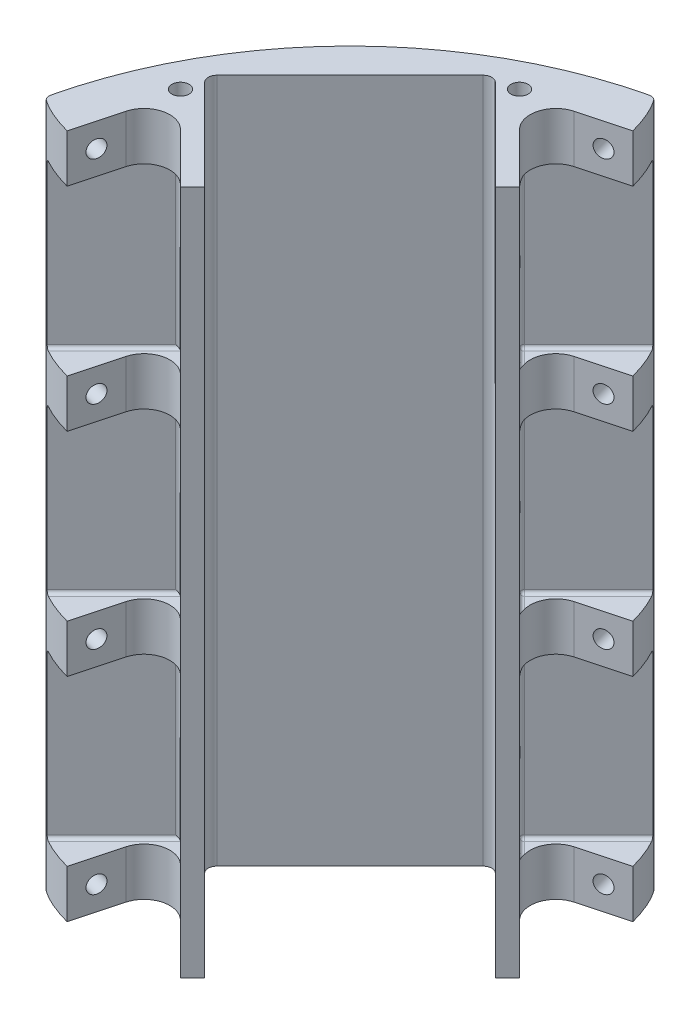
SolidWorks part; units mm, degrees
material "6061-T6 (SS)"
ref_plane "Front Plane" through (0, 0, 0) normal (0, 0, 1) x (1, 0, 0)
ref_plane "Top Plane" through (0, 0, 0) normal (0, 1, 0) x (1, 0, 0)
ref_plane "Right Plane" through (0, 0, 0) normal (1, 0, 0) x (0, 0, -1)
sketch "Constraints" plane through (0, 0, 0) normal (0, 1, 0) x (1, 0, 0)
  line L0 (0, 152.4) -> (0, -152.4) construction
  line L1 (-152.4, 0) -> (152.4, 0) construction
  circle A0 centre (0, 0) radius 152.4 construction
  circle A1 centre (0, 0) radius 149.225 construction
  circle A2 centre (0, 0) radius 12.7 construction
  circle A3 centre (0, 76.454) radius 12.7 construction
  circle A4 centre (76.454, 0) radius 12.7 construction
  circle A5 centre (0, -76.454) radius 12.7 construction
  circle A6 centre (-76.454, 0) radius 12.7 construction
  point P20 (0, 0)
  dimension "D1" = 25.4
  dimension "D4" = 304.8
  dimension "D3" = 76.454
  dimension "D2" = 3.175
  dimension "D6" = 76.454
  dimension "D7" = 76.454
  dimension "D5" = 4
sketch "Base" plane through (0, 0, 0) normal (0, 1, 0) x (1, 0, 0)
  line L0 (0, 76.454) -> (-76.454, 0) construction
  line L5 (21.8789, -21.8789) -> (-16.3481, 16.3481) construction
  line L9 (-27.6819, 146.635) -> (-55.7275, 118.5893)
  line L10 (-123.0795, 69.1979) -> (-87.1584, 33.2769)
  line L11 (-69.1979, 123.0795) -> (-123.0795, 69.1979)
  line L12 (-69.1979, 123.0795) -> (-33.2769, 87.1584)
  line L13 (-33.2769, 87.1584) -> (-28.7868, 91.6486)
  line L14 (-28.7868, 91.6486) -> (-55.7275, 118.5893)
  line L15 (-146.635, 27.6819) -> (-118.5893, 55.7275)
  line L16 (-91.6486, 28.7868) -> (-118.5893, 55.7275)
  line L17 (-87.1584, 33.2769) -> (-91.6486, 28.7868)
  line L18 (-19.5371, 78.1962) -> (-81.4004, 16.3329) construction
  arc A2 (-146.635, 27.6819) -> (-27.6819, 146.635) centre (0, 0) cw
  circle A3 centre (0, 0) radius 149.225 construction
  point P18 (-96.1387, 96.1387)
  dimension "D2" = 6.35
  dimension "D4" = 38.1
  dimension "D5" = 50.8
  dimension "D6" = 16.0528
  dimension "D3" = 76.2
  dimension "D1" = 68.619
extrude "Cradle" add sketch "Base" along normal blind 254 contours L9 L14 L13 L12 L11 L10 L17 L16 L15 A2
ref_plane "Mirror Plane 1" through (0, 127, 0) normal (0, 1, 0) x (1, 0, 0)
sketch "Sketch1" plane through (0, 254, 0) normal (0, 1, 0) x (1, 0, 0)
  line L1 (-69.1979, 123.0795) -> (-33.2769, 87.1584) construction
  line L2 (-69.1979, 123.0795) -> (-123.0795, 69.1979) construction
  line L3 (-69.1979, 123.0795) -> (-51.2374, 123.0795) construction
  line L4 (-96.1387, 96.1387) -> (-75.7363, 75.7363) construction
  line L5 (-27.6819, 146.635) -> (-55.7275, 118.5893) construction
  circle A0 centre (-60.2177, 123.0795) radius 3.175
  circle A2 centre (-123.0795, 60.2177) radius 3.175
  point P11 (-96.1387, 96.1387)
  dimension "D1" = 6.35
  dimension "D2" = 45
extrude "Cut-Extrude1" cut sketch "Sketch1" against normal blind 12.7 contours A2 | A0 region at (-123.0795, 254, -60.2177)
mirror "Mirror1" about plane through (0, 127, 0) normal (0, 1, 0) of "Cut-Extrude1"
ref_plane "Mirror Plane 2" through (0, 0, 0) normal (-0.7071, 0, 0.7071) x (0.7071, 0, 0.7071)
fillet "Eigth Inch Fillets (Internal)" radius 3.175 2 edges at (-123.0795, 127, -69.1979) (-69.1979, 127, -123.0795)
sketch "Sketch5" plane through (0, 0, 0) normal (0, -1, 0) x (1, 0, 0)
  line L0 (-1.749, -1.749) -> (-105.518, -105.518) construction
  line L1 (-159.3964, 6.0469) -> (-137.3575, -76.2032) construction
  line L2 (-131.3265, -0.5733) -> (-126.8165, -17.4048) construction
  line L3 (-71.443, -120.8344) -> (-120.8344, -71.443) construction
  line L4 (-116.9887, -31.347) -> (-128.5542, -34.446) construction
  line L5 (-126.122, -42.9979) -> (-130.7238, -25.8237)
  line L6 (-91.6486, -28.7868) -> (-118.5893, -55.7275) construction
  line L7 (-146.635, -27.6819) -> (-118.5893, -55.7275)
  line L8 (-118.5893, -55.7275) -> (-110.0025, -47.1408)
  arc A0 (-146.635, -27.6819) -> (-27.6819, -146.635) centre (0, 0) ccw construction
  circle A1 centre (0, 0) radius 152.4 construction
  circle A2 centre (0, 0) radius 149.225 construction
  arc A4 (-126.122, -42.9979) -> (-110.0025, -47.1408) centre (-116.8944, -40.5254) ccw
  arc A5 (-130.7238, -25.8237) -> (-146.635, -27.6819) centre (-145.018, 27.5232) cw
  point P4 (-53.6335, -53.6335)
  point P8 (-105.518, -105.518)
  point P11 (-96.1387, -96.1387)
  point P23 (-128.4229, -34.4108)
  line M18 (-118.5893, -55.7275) -> (-146.635, -27.6819)
  dimension "D1" = 304.8
  dimension "D2" = 25.4
  dimension "D3" = 5.9531
  dimension "D4" = 17.78
  dimension "D5" = 30
extrude "Radial Bolt Holder" add sketch "Sketch5" against normal blind 17.78 contours L5 A5 L8 A4 M18 region at (-131.0378, 0, -37.8112)
sketch "Sketch6" plane through (-128.4229, 0, -34.4108) normal (0.9659, 0, 0.2588) x (0.2588, 0, -0.9659)
  line L0 (-8.89, 17.78) -> (8.89, 0) construction
  circle A0 centre (0, 8.89) radius 3.175
  dimension "D1" = 6.35
extrude "Bolt Hole" cut sketch "Sketch6" against normal through all
pattern_linear "Pattern the Radial Bolt Holder" count 4 spacing 78.74 along (0, 1, 0) of "Radial Bolt Holder", "Bolt Hole"
mirror "Mirror Aforementioned Pattern" about plane through (0, 0, 0) normal (-0.7071, 0, 0.7071) of "Pattern the Radial Bolt Holder"
sketch "Sketch4" plane through (26.9408, 0, -26.9408) normal (-0.7071, 0, 0.7071) x (0.7071, 0, 0.7071)
  line L4 (-85.1607, 103.1875) -> (-85.1607, 150.8125) construction
  line L5 (-132.7857, 254) -> (-132.7857, 0) construction
  line L6 (-132.7857, 254) -> (-85.1607, 254) construction
  circle A0 centre (-108.9732, 127) radius 1.27
  circle A1 centre (-108.9732, 101.6) radius 1.27
  circle A2 centre (-108.9732, 76.2) radius 1.27
  circle A3 centre (-108.9732, 50.8) radius 1.27
  circle A4 centre (-108.9732, 25.4) radius 1.27
  circle A5 centre (-108.9732, 127) radius 1.27
  circle A6 centre (-108.9732, 101.6) radius 1.27
  circle A7 centre (-108.9732, 76.2) radius 1.27
  circle A8 centre (-108.9732, 50.8) radius 1.27
  circle A9 centre (-108.9732, 152.4) radius 1.27
  circle A10 centre (-108.9732, 127) radius 1.27
  circle A11 centre (-108.9732, 101.6) radius 1.27
  circle A12 centre (-108.9732, 76.2) radius 1.27
  circle A13 centre (-108.9732, 177.8) radius 1.27
  circle A14 centre (-108.9732, 152.4) radius 1.27
  circle A15 centre (-108.9732, 127) radius 1.27
  circle A16 centre (-108.9732, 101.6) radius 1.27
  circle A17 centre (-108.9732, 203.2) radius 1.27
  circle A18 centre (-108.9732, 177.8) radius 1.27
  circle A19 centre (-108.9732, 152.4) radius 1.27
  circle A20 centre (-108.9732, 127) radius 1.27
  circle A21 centre (-108.9732, 152.4) radius 1.27
  circle A22 centre (-108.9732, 177.8) radius 1.27
  circle A23 centre (-108.9732, 203.2) radius 1.27
  circle A25 centre (-96.2732, 25.4) radius 1.27
  circle A26 centre (-96.2732, 50.8) radius 1.27
  circle A27 centre (-96.2732, 76.2) radius 1.27
  circle A28 centre (-96.2732, 101.6) radius 1.27
  circle A29 centre (-96.2732, 127) radius 1.27
  circle A30 centre (-96.2732, 152.4) radius 1.27
  circle A31 centre (-96.2732, 177.8) radius 1.27
  circle A32 centre (-96.2732, 203.2) radius 1.27
  circle A33 centre (-96.2732, 228.6) radius 1.27
  circle A34 centre (-108.9732, 25.4) radius 1.27
  circle A35 centre (-108.9732, 50.8) radius 1.27
  circle A36 centre (-108.9732, 76.2) radius 1.27
  circle A37 centre (-108.9732, 101.6) radius 1.27
  circle A38 centre (-108.9732, 127) radius 1.27
  circle A39 centre (-108.9732, 152.4) radius 1.27
  circle A40 centre (-108.9732, 177.8) radius 1.27
  circle A41 centre (-108.9732, 203.2) radius 1.27
  circle A52 centre (-121.6732, 152.4) radius 1.27 [skipped]
  circle A53 centre (-121.6732, 177.8) radius 1.27 [skipped]
  circle A54 centre (-121.6732, 203.2) radius 1.27 [skipped]
  circle A55 centre (-108.9732, 228.6) radius 1.27
  circle A56 centre (-108.9732, 228.6) radius 1.27 [skipped]
  circle A57 centre (-121.6732, 101.6) radius 1.27 [skipped]
  circle A58 centre (-121.6732, 127) radius 1.27 [skipped]
  circle A59 centre (-121.6732, 25.4) radius 1.27 [skipped]
  circle A60 centre (-121.6732, 50.8) radius 1.27 [skipped]
  circle A61 centre (-121.6732, 76.2) radius 1.27 [skipped]
  dimension "D1" = 2.54
  dimension "D9" = 47.625
  dimension "D6" = 11.1125
  dimension "D7" = 23.8125
  dimension "D8" = 25.4
  dimension "D10" = 50.8
  dimension "D3" = 5
extrude "Wire Holes" cut sketch "Sketch4" against normal through all contours A4 | A25 | A3 | A26 | A2 | A27 | A1 | A28 | A0 | A29 | A9 | A30 | A13 | A31 | A17 | A32 | A33 | A55 region at (-50.1149, 127, -103.9964) region at (-50.1149, 101.6, -103.9964) region at (-50.1149, 76.2, -103.9964) region at (-50.1149, 50.8, -103.9964) region at (-50.1149, 25.4, -103.9964) region at (-50.1149, 152.4, -103.9964) region at (-50.1149, 177.8, -103.9964) region at (-50.1149, 203.2, -103.9964) region at (-41.1346, 25.4, -95.0162) region at (-41.1346, 50.8, -95.0162) region at (-41.1346, 76.2, -95.0162) region at (-41.1346, 101.6, -95.0162) region at (-41.1346, 127, -95.0162) region at (-41.1346, 152.4, -95.0162) region at (-41.1346, 177.8, -95.0162) region at (-41.1346, 203.2, -95.0162) region at (-41.1346, 228.6, -95.0162) region at (-50.1149, 228.6, -103.9964)
sketch "Sketch7" plane through (0, 0, 0) normal (0, -1, 0) x (1, 0, 0)
  line L0 (-127.6011, -37.4776) -> (-129.2446, -31.344) construction
  line L1 (-127.6011, -37.4776) -> (-129.2446, -31.344) construction
  line L2 (-129.2446, -31.344) -> (-144.9294, -35.5467) construction
  line L3 (-127.6011, -37.4776) -> (-143.2859, -41.6803) construction
  line L9 (-25.8237, -130.7238) -> (-42.9979, -126.122)
  line L10 (-47.4172, -110.279) -> (-28.7868, -91.6486)
  line L11 (-28.7868, -91.6486) -> (-33.2769, -87.1584)
  line L12 (-33.2769, -87.1584) -> (-66.9529, -120.8344)
  line L13 (-71.443, -120.8344) -> (-120.8344, -71.443)
  line L14 (-120.8344, -66.9529) -> (-87.1584, -33.2769)
  line L15 (-87.1584, -33.2769) -> (-91.6486, -28.7868)
  line L16 (-91.6486, -28.7868) -> (-110.279, -47.4172)
  line L17 (-126.122, -42.9979) -> (-130.7238, -25.8237)
  line L18 (-25.8237, -130.7238) -> (-42.9979, -126.122)
  line L19 (-47.4172, -110.279) -> (-28.7868, -91.6486)
  line L20 (-28.7868, -91.6486) -> (-33.2769, -87.1584)
  line L21 (-33.2769, -87.1584) -> (-66.9529, -120.8344)
  line L22 (-71.443, -120.8344) -> (-120.8344, -71.443)
  line L23 (-120.8344, -66.9529) -> (-87.1584, -33.2769)
  line L24 (-87.1584, -33.2769) -> (-91.6486, -28.7868)
  line L25 (-91.6486, -28.7868) -> (-110.279, -47.4172)
  line L26 (-126.122, -42.9979) -> (-130.7238, -25.8237)
  arc A0 (-144.9294, -35.5467) -> (-143.2859, -41.6803) centre (0, 0) ccw construction
  arc A1 (-144.9294, -35.5467) -> (-143.2859, -41.6803) centre (0, 0) ccw construction
  arc A7 (-146.635, -27.6819) -> (-27.6819, -146.635) centre (0, 0) ccw
  arc A8 (-25.8237, -130.7238) -> (-27.6819, -146.635) centre (27.5232, -145.018) ccw
  arc A9 (-47.4172, -110.279) -> (-42.9979, -126.122) centre (-40.5254, -116.8944) ccw
  arc A10 (-71.443, -120.8344) -> (-66.9529, -120.8344) centre (-69.1979, -118.5893) ccw
  arc A11 (-120.8344, -66.9529) -> (-120.8344, -71.443) centre (-118.5893, -69.1979) ccw
  arc A12 (-126.122, -42.9979) -> (-110.279, -47.4172) centre (-116.8944, -40.5254) ccw
  arc A13 (-146.635, -27.6819) -> (-130.7238, -25.8237) centre (-145.018, 27.5232) ccw
  arc A14 (-146.635, -27.6819) -> (-27.6819, -146.635) centre (0, 0) ccw
  arc A15 (-25.8237, -130.7238) -> (-27.6819, -146.635) centre (27.5232, -145.018) ccw
  arc A16 (-47.4172, -110.279) -> (-42.9979, -126.122) centre (-40.5254, -116.8944) ccw
  arc A17 (-71.443, -120.8344) -> (-66.9529, -120.8344) centre (-69.1979, -118.5893) ccw
  arc A18 (-120.8344, -66.9529) -> (-120.8344, -71.443) centre (-118.5893, -69.1979) ccw
  arc A19 (-126.122, -42.9979) -> (-110.279, -47.4172) centre (-116.8944, -40.5254) ccw
  arc A20 (-146.635, -27.6819) -> (-130.7238, -25.8237) centre (-145.018, 27.5232) ccw
  ellipse E0 centre (-129.2446, -31.344) end of major axis (-111.149, -26.4953) minor radius 5.715 (-147.3045, -36.3095) -> (-130.7238, -25.8237) cw
  arc M22 (-146.635, -27.6819) -> (-27.6819, -146.635) centre (0, 0) ccw
  arc M37 (-130.7238, -25.8237) -> (-146.635, -27.6819) centre (-145.018, 27.5232) cw
  dimension "D1" = 0
extrude "Weight Reducing Cut" cut sketch "Sketch7" against normal through all contours E0 M22 M37 region at (-142.4215, 0, -29.0288)
fillet "Bottom Edge Fillet" radius 2.54 1 edges at (-145.5925, 127, -32.725)
mirror "Mirror2" about plane through (0, 0, 0) normal (-0.7071, 0, 0.7071) of "Bottom Edge Fillet", "Weight Reducing Cut"
fillet "Fillets for Radial Bolt Holders" radius 1.27 24 edges at (-43.3683, 236.22, -130.9485) (-51.5724, 236.22, -114.4342) (-55.7275, 205.74, -118.5893) (-43.3683, 175.26, -130.9485) (-51.5724, 175.26, -114.4342) (-43.3683, 157.48, -130.9485) (-51.5724, 157.48, -114.4342) (-55.7275, 127, -118.5893) (-51.5724, 96.52, -114.4342) (-43.3683, 96.52, -130.9485) (-43.3683, 78.74, -130.9485) (-51.5724, 78.74, -114.4342) (-55.7275, 48.26, -118.5893) (-43.3683, 17.78, -130.9485) (-51.5724, 17.78, -114.4342) (-130.9485, 17.78, -43.3683) (-118.5893, 48.26, -55.7275) (-130.9485, 78.74, -43.3683) (-130.9485, 96.52, -43.3683) (-118.5893, 127, -55.7275) (-130.9485, 157.48, -43.3683) (-130.9485, 175.26, -43.3683) (-118.5893, 205.74, -55.7275) (-130.9485, 236.22, -43.3683)
equation "\"Pipe Diameter\"= 1in"
equation "\"D1@Constraints\"=\"Pipe Diameter\""
equation "\"Pipe Radial Distance\"= 3.01in"
equation "\"D3@Constraints\"=\"Pipe Radial Distance\""
equation "\"Rocket Diameter\"= 12in"
equation "\"D4@Constraints\"=\"Rocket Diameter\""
equation "\"Airframe Thickness\"= 0.125in"
equation "\"D2@Constraints\"=\"Airframe Thickness\""
equation "\"D6@Constraints\"=\"Pipe Radial Distance\""
equation "\"D7@Constraints\"=\"Pipe Radial Distance\""
equation "\"Arduino Mega Length\"= 101.52mm"
equation "\"Arduino Mega Width\"= 53.3mm"
equation "\"Interior Height\"= 2in"
equation "\"Wall Thickness\"= 0.5in"
equation "\"Assembly Hole Diameter\"= 0.25in"
equation "\"D2@Base\"=\"Wall Thickness\"*0.5"
equation "\"D4@Base\" = \"Interior Height\" - \"Wall Thickness\""
equation "\"D5@Base\" = \"Interior Height\""
equation "\"4-40 Standoff Depth\"= 0.1875in"
equation "\"D1@Cradle\"=10in"
equation "\"D1@Sketch1\"=\"Assembly Hole Diameter\""
equation "\"D1@Cut-Extrude1\"=\"Wall Thickness\""
equation "\"D1@Eigth Inch Fillets (Internal)\" = 0.5 * \"Assembly Hole Diameter\""
equation "\"Wire Hole Diameter\"= 0.1in"
equation "\"D1@Sketch4\"= \"Wire Hole Diameter\""
equation "\"Flange Nut Height\"= 15 / 64in"
equation "\"Flange Nut Diameter\"= 19 / 32in"
equation "\"Assembly Bolt Length\"= 1in"
equation "\"D1@Sketch5\"=\"Rocket Diameter\""
equation "\"D3@Sketch5\"=\"Flange Nut Height\""
equation "\"D1@Sketch6\"=\"Assembly Hole Diameter\""
